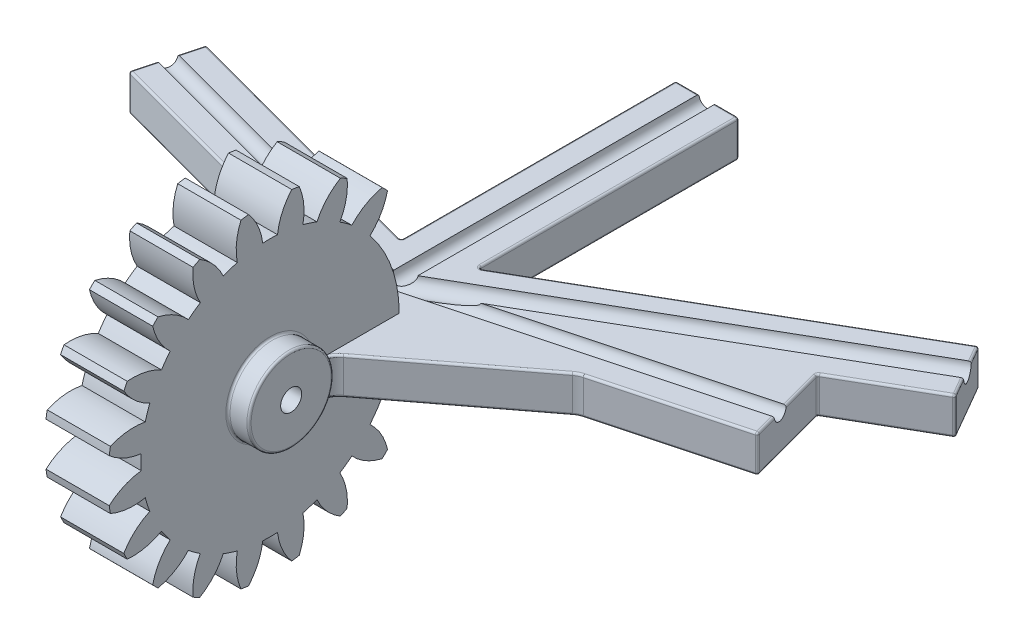
SolidWorks part; units mm, degrees
ref_plane "Plane1" through (0, 0, 0) normal (0, 0, 1) x (1, 0, 0)
ref_plane "Plane2" through (0, 0, 0) normal (0, 1, 0) x (1, 0, 0)
ref_plane "Plane3" through (0, 0, 0) normal (1, 0, 0) x (0, 0, -1)
other "Configuration Table"
sketch "HoldingSke" plane through (0, 0, 0) normal (0, 1, 0) x (1, 0, 0)
  line L0 (0, 0) -> (1.3424, -0.4886)
  line L1 (-15, 0) -> (100, 0) construction
  line L2 (0, 0) -> (-2.1039, 2.3779)
  line L3 (0, 0) -> (-11.863, 4.5341)
  line L4 (0, 0) -> (8.1152, 2.9537)
  line L5 (0, 0) -> (-46.8476, -17.4728)
  line L6 (0, 0) -> (-2.4869, -1.6779)
  line L7 (-2.1039, 2.3779) -> (8.6586, 51.2059)
  line L8 (-76.2, 54.61) -> (-76.1, 54.61)
  line L9 (-71.009, 38.7566) -> (-53.1078, 45.2721)
  line L10 (-76.2, 71.12) -> (104.1128, 71.12)
  line L11 (0, 0) -> (-3, 0)
  line L12 (-76.2, 101.6) -> (-76.173, 101.6)
  line L13 (24.9733, 27.94) -> (52.9518, 28.4284)
  line L14 (24.9733, 27.94) -> (24.9743, 27.94)
  line L15 (24.9733, 27.94) -> (100.4006, 29.5858)
  line L16 (-63.627, -0.7) -> (-12.827, -0.7)
  circle A0 centre (0, 0) radius 0.5
  circle A1 centre (0, 0) radius 6.124
  circle A2 centre (0, 0) radius 37.5
  circle A3 centre (0, 0) radius 0.5
  dimension "Num_teeth" = 20
  dimension "Pitch_radius" = 180.3128
  dimension "Width" = 3
  dimension "Thickness" = 3
sketch "BasProSke" plane through (0, 0, 0) normal (0, 1, 0) x (1, 0, 0)
  line L0 (-10, 0) -> (60, 0) construction
  line L1 (0, 0) -> (0, 7.7)
  line L2 (0, 0) -> (3, 0)
  line L3 (3, 0) -> (3, 7.7)
  line L4 (3, 7.7) -> (0, 7.7)
  dimension "Thickness" = 3
  dimension "Diameter" = 15.4
revolve "Base-Revolve" add sketch "BasProSke" angle 360 about L0
sketch "TooCutSke" plane through (0, 0, 0) normal (1, 0, 0) x (0, 0, -1)
  line L1 (0, 0) -> (0, 107) construction
  line L2 (0, 0) -> (-0.5964, 6.9745) construction
  line L3 (0, 0) -> (-2.1844, 13.792) construction
  line L4 (-0.5964, 6.9745) -> (-1.0922, 6.896) construction
  arc A0 (0.3505, 6.114) -> (-0.3505, 6.114) centre (0, 0) ccw
  arc A1 (1.0465, 7.6542) -> (-1.0465, 7.6542) centre (0, 0) ccw
  circle A2 centre (0, 0) radius 7 construction
  circle A3 centre (0, 0) radius 6.5778 construction
  arc A4 (-0.3505, 6.114) -> (-1.0465, 7.6542) centre (-3.1311, 5.7848) ccw
  arc A5 (1.0465, 7.6542) -> (0.3505, 6.114) centre (3.1311, 5.7848) ccw
extrude "ToothCut" cut sketch "TooCutSke" along normal through all
fillet "Breaks" [suppressed] radius 0.014 tangent propagation no
fillet "RootFillets" [suppressed] radius 0.176
pattern_circular "TeethCuts" count 20 every 18 about axis through (-10, 0, 0) along (1, 0, 0) of "ToothCut", "RootFillets", "Breaks"
sketch "HubNeaOneSke" plane through (0, 0, 0) normal (-1, 0, 0) x (0, 0, 1)
  circle A0 centre (0, 0) radius 6.124
  dimension "Diameter" = 12.248
extrude "HubNearOne" [suppressed] add sketch "HubNeaOneSke" along normal blind 47.0001
sketch "HubNeaBotSke" plane through (0, 0, 0) normal (-1, 0, 0) x (0, 0, 1)
  circle A0 centre (0, 0) radius 6.124
  dimension "Diameter" = 12.248
extrude "HubNearBoth" [suppressed] add sketch "HubNeaBotSke" along normal blind 23.5
ref_plane "FarPln" through (3, 0, 0) normal (1, 0, 0) x (0, 0, -1)
sketch "HubFarSke" plane through (3, 0, 0) normal (1, 0, 0) x (0, 0, -1)
  circle A0 centre (0, 0) radius 6.124
  dimension "Diameter" = 12.248
extrude "HubFar" [suppressed] add sketch "HubFarSke" along normal blind 23.5
sketch "BorSke" plane through (0, 0, 0) normal (1, 0, 0) x (0, 0, -1)
  circle A0 centre (0, 0) radius 0.5
  dimension "Diameter" = 1
extrude "Bore" cut sketch "BorSke" along normal mid plane 100.0001
sketch "KeySke" plane through (0, 0, 0) normal (1, 0, 0) x (0, 0, -1)
  line L0 (-0.05, 0) -> (-0.05, 0.6)
  line L1 (-0.05, 0.6) -> (0.05, 0.6)
  line L2 (0.05, 0.6) -> (0.05, 0)
  line L3 (0, 0) -> (0, 34) construction
  line L4 (-0.05, 0) -> (0.05, 0)
extrude "Keyway" [suppressed] cut sketch "KeySke" along normal mid plane 100.0001
pattern_circular "Keyway2" [suppressed] count 2 every 90 about axis through (-10, 0, 0) along (1, 0, 0)
sketch "草图1" plane through (3, 0, 0) normal (1, 0, 0) x (0, 0, -1)
  line L0 (4.9544, 3.5996) -> (6.3295, 4.5987)
  line L1 (4.9544, -3.5996) -> (6.3295, -4.5987)
  arc A0 (4.9544, 3.5996) -> (4.9544, -3.5996) centre (0, 0) cw
  arc A1 (5.1523, 3.3101) -> (4.7403, 3.8773) centre (0, 0) ccw construction
  arc A2 (4.7403, -3.8773) -> (5.1523, -3.3101) centre (0, 0) ccw construction
  arc A3 (6.3295, 4.5987) -> (6.3295, -4.5987) centre (-0.1229, 0) cw
extrude "切除-拉伸1" cut sketch "草图1" against normal through all
sketch "草图3" plane through (0, 0, 0) normal (0, 1, 0) x (1, 0, 0)
  line L0 (1.5, 6.0932) -> (1.5, 22.2442) construction
  line L2 (0, 6.0932) -> (3, 6.0932)
  line L3 (0, 6.124) -> (0, 4.7403) construction
  line L4 (3, 4.7403) -> (3, 6.124) construction
  line L5 (1.5, 7.2442) -> (-12.9889, 11.1265) construction
  line L6 (1.5, 7.2442) -> (18.8205, 17.2442) construction
  line L7 (1.5, 7.2442) -> (15.9889, 11.1265) construction
  line L8 (-12.6007, 12.5754) -> (-13.3771, 9.6776)
  line L9 (-13.3771, 9.6776) -> (0, 6.0932)
  line L10 (-12.6007, 12.5754) -> (0, 9.1991)
  line L11 (0, 9.1991) -> (0, 22.2442)
  line L12 (0, 22.2442) -> (3, 22.2442)
  line L13 (3, 22.2442) -> (3, 9.8423)
  line L14 (3, 9.8423) -> (18.0705, 18.5433)
  line L15 (18.0705, 18.5433) -> (19.5705, 15.9452)
  line L16 (19.5705, 15.9452) -> (15.4137, 13.5453)
  line L18 (15.4137, 13.5453) -> (16.4448, 9.6975)
  line L19 (16.4448, 9.6975) -> (3, 6.0949)
  line L20 (3, 6.0949) -> (3, 6.0932)
  dimension "D1" = 75
  dimension "D2" = 3
  dimension "D3" = 15
  dimension "D4" = 15
  dimension "D5" = 60
  dimension "D6" = 15
  dimension "D7" = 20
  dimension "D8" = 15
  dimension "D9" = 3
  dimension "D10" = 1.5
extrude "凸台-拉伸1" add sketch "草图3" against normal blind 1.75
sketch "草图4" plane through (0, 0, 0) normal (-1, 0, 0) x (0, 0, 1)
  line L0 (-6.0932, 0) -> (-6.0932, -1.75)
  line L1 (-6.0932, -1.75) -> (-5.6573, -2.3449)
  arc A0 (-6.0932, -0.6132) -> (-4.7403, -3.8773) centre (0, 0) ccw construction
  arc A1 (-5.6573, -2.3449) -> (-6.0932, 0) centre (127.3235, 23.5911) cw
extrude "凸台-拉伸3" add sketch "草图4" against normal blind 3
sketch "草图6" plane through (0, 0, 0) normal (0, 1, 0) x (1, 0, 0)
  line L0 (9.7224, 7.8962) -> (3, 2.7784)
  line L1 (3, 6.0949) -> (16.4448, 9.6975) construction
  line L2 (3, 2.2227) -> (3, 3.3342) construction
  line L3 (0, 2.7784) -> (-6.6886, 7.8854)
  line L4 (0, 3.3342) -> (0, 2.2227) construction
  line L5 (-13.3771, 9.6776) -> (0, 6.0932) construction
  line L6 (-6.6886, 7.8854) -> (0, 6.0932)
  line L7 (0, 6.0932) -> (0, 2.7784)
  line L8 (9.7224, 7.8962) -> (3, 6.0949)
  line L9 (3, 6.0949) -> (3, 2.7784)
extrude "凸台-拉伸5" add sketch "草图6" against normal blind 1.75
sketch "草图9" plane through (0, 0, -22.2442) normal (0, 0, -1) x (-1, 0, 0)
  line L0 (-3, 0) -> (0, 0) construction
  circle A0 centre (-1.5, 0) radius 0.4
sketch "草图10" plane through (-14.9004, 0, -3.9926) normal (-0.9659, 0, -0.2588) x (-0.2588, 0, 0.9659)
  line L0 (-8.8856, 0) -> (-5.8856, 0) construction
  circle A0 centre (-7.3856, 0) radius 0.4
fillet "圆角4" radius 0.1 18 edges at (17.4921, -1.75, -14.7452) (17.4921, 0, -14.7452) (-12.9889, 0, -11.1265) (-12.9889, -1.75, -11.1265) (-12.6007, -0.875, -12.5754) (-13.3771, -0.875, -9.6776) (1.5, -1.75, -22.2442) (3, -0.875, -22.2442) (0, -0.875, -22.2442) (1.5, 0, -22.2442) (18.8205, -1.75, -17.2442) (18.0705, -0.875, -18.5433) (18.8205, 0, -17.2442) (19.5705, -0.875, -15.9452) (15.9293, -1.75, -11.6214) (15.9293, 0, -11.6214) (15.4137, -0.875, -13.5453) (16.4448, -0.875, -9.6975)
fillet "圆角6" radius 1 1 edges at (9.7224, -0.875, -7.8962)
fillet "圆角7" radius 1 1 edges at (3, -0.875, -2.7784)
fillet "圆角8" radius 1 2 edges at (-6.6886, -0.875, -7.8854) (0, -0.875, -2.7784)
fillet "圆角9" radius 0.1 10 edges at (-0.1037, 0, -2.7272) (-0.1037, -1.75, -2.7272) (-3.4623, 0, -5.422) (-3.4623, -1.75, -5.422) (-13.3412, -0.0293, -9.6983) (-10.08, 0, -8.7942) (-6.6971, 0, -7.8681) (-13.3412, -1.7207, -9.6983) (-10.08, -1.75, -8.7942) (-6.6971, -1.75, -7.8681)
fillet "圆角10" radius 0.1 10 edges at (3.104, -1.75, -2.7269) (3.104, 0, -2.7269) (6.48, -1.75, -5.4278) (6.48, 0, -5.4278) (16.4089, -1.7207, -9.7182) (13.1304, -1.75, -8.8094) (9.7308, -1.75, -7.879) (16.4089, -0.0293, -9.7182) (13.1304, 0, -8.8094) (9.7308, 0, -7.879)
sketch "草图14" plane through (0, 0, 0) normal (-1, 0, 0) x (0, 0, 1)
  circle A0 centre (0, 0) radius 2
  circle A1 centre (0, 0) radius 0.5
extrude "凸台-拉伸7" add sketch "草图14" along normal blind 1
sketch "草图15" plane through (3, 0, 0) normal (1, 0, 0) x (0, 0, -1)
  circle A0 centre (0, 0) radius 2
  circle A1 centre (0, 0) radius 0.5
extrude "凸台-拉伸8" add sketch "草图15" along normal blind 1
fillet "圆角11" radius 0.1 1 edges at (4, 0, -2)
fillet "圆角12" radius 0.1 2 edges at (0, 0, -2) (-1, 0, 2)
fillet "圆角13" radius 0.1 1 edges at (3, 0, 2)
sketch "草图16" plane through (21.5823, 0, -12.4606) normal (0.866, 0, -0.5) x (-0.5, 0, -0.866)
  line L0 (4.1237, 0) -> (7.0237, 0) construction
  circle A0 centre (5.5737, 0) radius 0.5
  point P0 (5.5737, 0)
sketch "草图17" plane through (17.7675, 0, -4.7608) normal (0.9659, 0, -0.2588) x (-0.2588, 0, -0.9659)
  line L0 (5.2108, 0) -> (9.0176, 0) construction
  line L1 (5.1108, -1.65) -> (5.1108, -0.1) construction
  circle A0 centre (6.6108, 0) radius 0.4
  point P0 (6.6108, 0)
  dimension "D1" = 1.5
extrude "切除-拉伸2" cut sketch "草图9" against normal blind 15
extrude "切除-拉伸3" cut sketch "草图10" against normal blind 15
extrude "切除-拉伸4" cut sketch "草图16" against normal blind 20
extrude "切除-拉伸5" cut sketch "草图17" against normal blind 15
fillet "圆角14" radius 0.1 18 edges at (0.0293, -1.7207, -22.2149) (0.0293, -0.0293, -22.2149) (-12.5799, -0.0293, -12.5395) (-12.5799, -1.7207, -12.5395) (2.9707, -0.0293, -22.2149) (2.9707, -1.7207, -22.2149) (18.0598, -1.7207, -18.5032) (18.0598, -0.0293, -18.5032) (0, -1.75, -15.6716) (0, 0, -15.6716) (0, -0.875, -9.1991) (-6.252, 0, -10.8743) (-6.252, -1.75, -10.8743) (3, 0, -15.9933) (3, -1.75, -15.9933) (3, -0.875, -9.8423) (10.492, -1.75, -14.1678) (10.492, 0, -14.1678)
equation "' \"Module@HoldingSke\" = 6.35"
equation "' \"Num_teeth@HoldingSke\" = 12"
equation "' \"Ap@HoldingSke\" =  20"
equation "' \"Ap@HoldingSke\" = 20"
equation "' \"Width@HoldingSke\" = 0.5 * 25.4"
equation "' \"Hub_dia@HoldingSke\"= 1 * 25.4"
equation "' \"Hub_dia@HoldingSke\" = 1 * 25.4"
equation "' \"Overall_len@HoldingSke\" = 1.0 * 25.4"
equation "' \"Bore@HoldingSke\" = 0.75 * 25.4"
equation "' \"T_dim@HoldingSke\" = 0.1 * 25.4"
equation "' \"Width@KeySke\" = 0.25 * 25.4"
equation "' \"Show_teeth@HoldingSke\" = 13"
equation "' \"Backlash@HoldingSke\" = 0.009 * 25.4"
equation "' \"Addendum_fac@HoldingSke\" = 1.0"
equation "' \"Dedendum_fac@HoldingSke\" = 1.25"
equation "' \"Dedendum_add@HoldingSke\" = 0.00005 * 25.4"
equation "' \"Clearance_fac@HoldingSke\" = 0.25"
equation "\"Pitch@HoldingSke\" = 1 / \"Module@HoldingSke\""
equation "\"Overcut_dia@TooCutSke\" = (\"Num_teeth@HoldingSke\" + 2 * \"Addendum_fac@HoldingSke\") / \"Pitch@HoldingSke\" + 0.002 * 25.4"
equation "\"Pitch_dia@TooCutSke\" = \"Num_teeth@HoldingSke\" / \"Pitch@HoldingSke\""
equation "\"Base_dia@TooCutSke\" = \"Num_teeth@HoldingSke\" / \"Pitch@HoldingSke\" * cos((\"Ap@HoldingSke\"  * 3.14159265 / 180))"
equation "\"Root_dia@TooCutSke\" = (\"Num_teeth@HoldingSke\" + 2) / \"Pitch@HoldingSke\" - 2 * (\"Addendum_fac@HoldingSke\" + \"Dedendum_fac@HoldingSke\") / \"Pitch@HoldingSke\" - \"Dedendum_add@HoldingSke\" * 2"
equation "\"Half_ang@TooCutSke\" = 180 / \"Num_teeth@HoldingSke\""
equation "\"Half_CT@TooCutSke\" = \"Num_teeth@HoldingSke\" / \"Pitch@HoldingSke\" * sin((3.14159265 / 2 / \"Num_teeth@HoldingSke\")) / 2 - 7 * \"Backlash@HoldingSke\" / 4"
equation "\"Flank_rad@TooCutSke\" = \"Num_teeth@HoldingSke\" / \"Pitch@HoldingSke\" / 5"
equation "\"Radius@RootFillets\" = \"Clearance_fac@HoldingSke\" / \"Pitch@HoldingSke\" + \"Dedendum_add@HoldingSke\""
equation "\"Break_rad@Breaks\" = 0.02 / \"Pitch@HoldingSke\""
equation "\"Thickness@HoldingSke\" = \"Width@HoldingSke\""
equation "\"OAL@HoldingSke\" = \"Thickness@HoldingSke\""
equation "\"MHD@HoldingSke\" = (\"Num_teeth@HoldingSke\" + 2) / \"Pitch@HoldingSke\" - 2 * (\"Addendum_fac@HoldingSke\" + \"Dedendum_fac@HoldingSke\")  / \"Pitch@HoldingSke\" - \"Dedendum_add@HoldingSke\" * 2"
equation "\"MBD@HoldingSke\" = (\"Num_teeth@HoldingSke\" + 2) / \"Pitch@HoldingSke\" - 2 * (\"Addendum_fac@HoldingSke\" + \"Dedendum_fac@HoldingSke\")  / \"Pitch@HoldingSke\" - \"Dedendum_add@HoldingSke\" * 2 - 0.002 * 25.4"
equation "\"MHD@HoldingSke\" = ((sgn( \"MHD@HoldingSke\" - \"Hub_dia@HoldingSke\" )-1)*( \"MHD@HoldingSke\" - \"Hub_dia@HoldingSke\" ))/-2+ \"Hub_dia@HoldingSke\""
equation "\"MBD@HoldingSke\" = ((sgn( \"MBD@HoldingSke\" - \"Bore@HoldingSke\" )-1)*( \"MBD@HoldingSke\" - \"Bore@HoldingSke\" ))/-2+ \"Bore@HoldingSke\""
equation "\"OAL@HoldingSke\" = ((sgn( \"OAL@HoldingSke\" - \"Overall_len@HoldingSke\" )+1)*( \"OAL@HoldingSke\" - \"Overall_len@HoldingSke\" ))/2 + \"Overall_len@HoldingSke\" + 0.000002 * 25.4"
equation "\"Num_teeth@TeethCuts\" = int( \"Show_teeth@HoldingSke\" ) + 1"
equation "\"Num_teeth@TeethCuts\" = ((sgn( \"Num_teeth@TeethCuts\" - \"Num_teeth@HoldingSke\" )-1)*( \"Num_teeth@TeethCuts\" - \"Num_teeth@HoldingSke\" ))/-2+ \"Num_teeth@HoldingSke\""
equation "\"Num_teeth@TeethCuts\" = ((sgn( \"Num_teeth@TeethCuts\" - 2.0)+1)*( \"Num_teeth@TeethCuts\" - 2.0))/2 +2.0"
equation "\"Angle@TeethCuts\" = 360.0 / \"Num_teeth@HoldingSke\""
equation "\"Diameter@BasProSke\" = (\"Num_teeth@HoldingSke\" + 2 * \"Addendum_fac@HoldingSke\") / \"Pitch@HoldingSke\""
equation "\"Thickness@BasProSke\"  = \"Thickness@HoldingSke\""
equation "' \"Fillet_rad@BasProSke\" =  \"Thickness@HoldingSke\" * 0.05"
equation "' \"Fillet_rad@BasProSke\" = \"Thickness@HoldingSke\" * 0.05"
equation "\"MHD@HoldingSke\" = ((sgn( \"MHD@HoldingSke\" - \"Root_dia@TooCutSke\" )-1)*( \"MHD@HoldingSke\" - \"Root_dia@TooCutSke\" ))/-2+ \"Root_dia@TooCutSke\""
equation "\"Diameter@HubNeaOneSke\" = \"MHD@HoldingSke\""
equation "\"Length@HubNearOne\" = \"OAL@HoldingSke\" - \"Thickness@BasProSke\""
equation "\"Diameter@HubNeaBotSke\" = \"MHD@HoldingSke\""
equation "\"Length@HubNearBoth\" = ( \"OAL@HoldingSke\" - \"Thickness@BasProSke\" ) / 2.0"
equation "\"Thickness@FarPln\" = \"Thickness@BasProSke\""
equation "\"Diameter@HubFarSke\" = \"MHD@HoldingSke\""
equation "\"Length@HubFar\" = ( \"OAL@HoldingSke\" - \"Thickness@BasProSke\" ) / 2.0"
equation "\"Diameter@BorSke\" = \"MBD@HoldingSke\""
equation "\"D1@Bore\" = \"OAL@HoldingSke\" * 2.0"
equation "\"D1@Keyway\" = \"OAL@HoldingSke\" * 2.0"
equation "\"Offset@KeySke\" = \"T_dim@HoldingSke\" + \"MBD@HoldingSke\" / 2.0"
